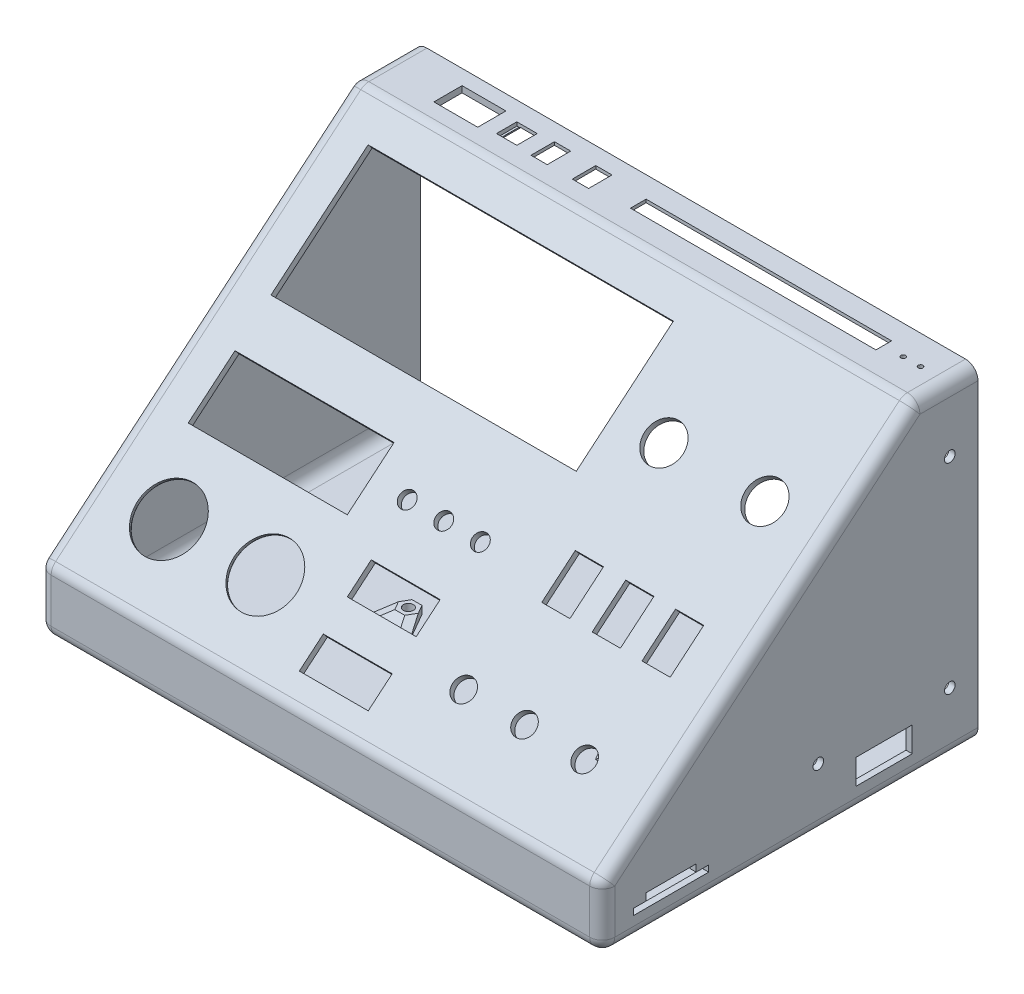
SolidWorks part; units mm, degrees
ref_plane "Front Plane" through (0, 0, 0) normal (0, 0, 1) x (1, 0, 0)
ref_plane "Top Plane" through (0, 0, 0) normal (0, 1, 0) x (1, 0, 0)
ref_plane "Right Plane" through (0, 0, 0) normal (1, 0, 0) x (0, 0, -1)
sketch "Sketch1" plane through (0, 0, 0) normal (0, 1, 0) x (1, 0, 0)
  line L1 (-90, -60) -> (90, -60)
  line L2 (-90, -60) -> (-90, 60)
  line L3 (-90, 60) -> (90, 60)
  line L4 (90, -60) -> (90, 60)
  line L5 (-90, -60) -> (90, 60) construction
  line L6 (-90, 60) -> (90, -60) construction
  point P0 (0, 0)
  dimension "D1" = 180
  dimension "D2" = 120
extrude "Boss-Extrude1" add sketch "Sketch1" along normal blind 20
sketch "Sketch2" plane through (-90, 0, 0) normal (-1, 0, 0) x (0, 0, 1)
  line L0 (60, 20) -> (-40, 103.91)
  line L1 (-60, 20) -> (60, 20) construction
  line L2 (60, 20) -> (60, 0) construction
  line L3 (-60, 20) -> (-60, 103.91)
  line L4 (-60, 103.91) -> (-40, 103.91)
  line L5 (-60, 20) -> (60, 20)
  dimension "D1" = 40
  dimension "D2" = 100
extrude "Boss-Extrude2" add sketch "Sketch2" against normal up to surface (180 mm away) up to face at (90, 10, 0)
shell "Shell3" thickness 2 removed face at (0, 51.955, -60)
fillet "Fillet1" radius 4 11 edges at (-90, 10, 60) (90, 10, 60) (0, 0, 60) (0, 20, 60) (-90, 61.955, 10) (0, 103.91, -40) (90, 61.955, 10) (-90, 103.91, -50) (-90, 0, 0) (90, 0, 0) (90, 103.91, -50)
fillet "Fillet2" radius 4 11 edges at (88, 10.5337, 58) (0, 19.0674, 58) (-88, 10.5337, 58) (0, 2, 58) (88, 101.91, -50.364) (0, 101.91, -40.7279) (-88, 101.91, -50.364) (88, 60.4887, 8.636) (88, 2, -1) (-88, 60.4887, 8.636) (-88, 2, -1)
sketch "Sketch7" plane through (0, 103.91, 0) normal (0, 1, 0) x (1, 0, 0)
  line L0 (-86, 60) -> (-86, 41.4559) construction
  line L1 (-86, 41.4559) -> (-86, 50.7279) construction
  line L2 (-86, 50.7279) -> (-56, 50.7279) construction
  line L3 (-56, 46.2279) -> (-56, 55.2279)
  line L4 (-56, 55.2279) -> (-70, 55.2279)
  line L5 (-70, 55.2279) -> (-70, 46.2279)
  line L6 (-70, 46.2279) -> (-56, 46.2279)
  point P9 (-56, 50.7279)
  dimension "D1" = 9
  dimension "D2" = 14
  dimension "D3" = 30
extrude "Cut-Extrude3" cut sketch "Sketch7" against normal up to next
sketch "Sketch8" plane through (0, 41.2807, 34.6386) normal (0, 0.766, 0.6428) x (1, 0, 0)
  line L0 (-86, 95.9779) -> (86, 95.9779) construction
  line L1 (86, 95.9779) -> (86, -31.2417) construction
  line L2 (86, -31.2417) -> (-86, -31.2417) construction
  line L3 (-86, -31.2417) -> (-86, 95.9779) construction
  line L4 (-76, 95.9779) -> (-76, -31.2417)
  line L5 (-86, 85.9779) -> (86, 85.9779)
  line L6 (86, -31.2417) -> (86, 95.9779) construction
  line L7 (-86, -31.2417) -> (86, -31.2417) construction
  line L8 (76, -31.2417) -> (76, 95.9779)
  line L9 (86, -21.2417) -> (-86, -21.2417)
  line L10 (-86, 95.9779) -> (-86, -31.2417) construction
  line L11 (86, 95.9779) -> (-86, 95.9779) construction
  line L12 (-73.5, 95.9779) -> (-73.5, 93.4779)
  line L13 (-76, 85.9779) -> (21.5, 85.9779)
  line L14 (-76, 85.9779) -> (-76, 45.4779)
  line L15 (-76, 45.4779) -> (21.5, 45.4779)
  line L16 (21.5, 85.9779) -> (21.5, 45.4779)
  line L17 (-76, 85.9779) -> (21.5, 85.9779) construction
  line L18 (-27.25, 85.9779) -> (-27.25, 45.4779) construction
  line L19 (-45.177, 65.7279) -> (-9.323, 65.7279)
  circle A0 centre (-73.5, 93.4779) radius 1.35
  circle A1 centre (-73.5, 37.9779) radius 1.35
  circle A2 centre (19, 37.9779) radius 1.35
  circle A3 centre (19, 93.4779) radius 1.35
  point P36 (-27.25, 65.7279)
  dimension "D1" = 10
  dimension "D2" = 10
  dimension "D3" = 10
  dimension "D4" = 10
  dimension "D5" = 97.5
  dimension "D6" = 40.5
  dimension "D7" = 2.5
  dimension "D8" = 2.5
extrude "Boss-Extrude4" add sketch "Sketch8" against normal blind 5 contours A0 | A3 | A2 | A1
extrude "Cut-Extrude4" cut sketch "Sketch8<3>" against normal blind 5 contours L16 L5 L4 L15 region at (-27.25, 95.8676, -30.4155)
sketch "Sketch8<3>" plane through (0, 41.2807, 34.6386) normal (0, 0.766, 0.6428) x (1, 0, 0) same geometry as "Sketch8"
sketch "Sketch9" plane through (0, 41.2807, 34.6386) normal (0, 0.766, 0.6428) x (1, 0, 0)
  line L0 (-76, 85.9779) -> (-76, 30.4779)
  line L1 (-76, 45.4779) -> (21.5, 45.4779) construction
  line L3 (-76, 30.4779) -> (-25.2, 30.4779)
  line L4 (-76, 30.4779) -> (-76, 10.9779)
  line L5 (-76, 10.9779) -> (-25.2, 10.9779)
  line L6 (-25.2, 30.4779) -> (-25.2, 10.9779)
  dimension "D1" = 15
  dimension "D2" = 50.8
  dimension "D3" = 19.5
extrude "Cut-Extrude5" cut sketch "Sketch9" against normal blind 5 contours L6 L3 L4 L5 region at (-50.6, 54.6044, 18.7601)
sketch "Sketch10" plane through (0, 41.2807, 34.6386) normal (0, 0.766, 0.6428) x (1, 0, 0)
  line L0 (-25.2, 30.4779) -> (-25.2, 10.9779) construction
  line L1 (21.5, 45.4779) -> (21.5, 10.9779)
  line L2 (-25.2, 30.4779) -> (21.5, 30.4779) construction
  line L3 (21.5, 30.4779) -> (21.5, 10.9779) construction
  line L4 (21.5, 10.9779) -> (-25.2, 10.9779) construction
  line L5 (-13.525, 20.7279) -> (-1.85, 20.7279)
  line L6 (-1.85, 20.7279) -> (9.825, 20.7279)
  circle A0 centre (-1.85, 20.7279) radius 2.525
  circle A1 centre (-13.525, 20.7279) radius 2.525
  circle A2 centre (9.825, 20.7279) radius 2.525
  dimension "D1" = 9.75
extrude "Cut-Extrude6" cut sketch "Sketch10" against normal blind 5 contours A1 | A0 | A2 | A0 region at (9.825, 56.1815, 16.8806) region at (-1.85, 55.2932, 17.9392) region at (-15.9786, 54.6044, 18.7601)
sketch "Sketch11" plane through (0, 41.2807, 34.6386) normal (0, 0.766, 0.6428) x (1, 0, 0)
  line L0 (21.5, 85.9779) -> (21.5, 45.4779) construction
  line L1 (86, 95.9779) -> (-86, 95.9779) construction
  line L2 (21.5, 65.7279) -> (86, 65.7279) construction
  line L3 (86, -31.2417) -> (86, 95.9779) construction
  line L4 (86, 65.7279) -> (53.75, 65.7279) construction
  line L5 (53.75, 65.7279) -> (21.5, 65.7279) construction
  line L6 (69.875, 67.1029) -> (69.875, 54.8529)
  line L7 (86, 65.7279) -> (53.75, 65.7279) construction
  line L8 (53.75, 65.7279) -> (86, 65.7279) construction
  line L9 (86, 65.7279) -> (69.875, 65.7279) construction
  line L10 (69.875, 65.7279) -> (69.875, 60.9779) construction
  line L11 (53.75, 65.7279) -> (53.75, 56.7637)
  circle A0 centre (69.875, 60.9779) radius 6.125
  circle A1 centre (37.625, 60.9779) radius 6.125
  dimension "D1" = 12.25
  dimension "D2" = 35
extrude "Cut-Extrude7" cut sketch "Sketch11" against normal blind 5 contours A1 | L6 A0 | L6 A0 region at (72.4745, 80.4766, -12.0732) region at (67.2755, 80.4766, -12.0732) region at (37.625, 80.4766, -12.0732)
sketch "Sketch12" plane through (0, 41.2807, 34.6386) normal (0, 0.766, 0.6428) x (1, 0, 0)
  line L0 (-76, 10.9779) -> (-76, -4.0221)
  line L1 (-76, -31.2417) -> (-76, -16.2417)
  line L2 (-86, -31.2417) -> (86, -31.2417) construction
  line L3 (-76, -4.0221) -> (-76, -16.2417) construction
  line L4 (-25.2, 10.9779) -> (-25.2, -31.2417)
  line L5 (-25.2, 30.4779) -> (-25.2, 10.9779) construction
  line L6 (-25.2, -31.2417) -> (-25.2, -10.1319)
  line L7 (-25.2, -10.1319) -> (-76, -10.1319)
  line L8 (-50.6, -10.1319) -> (-76, -10.1319) construction
  line L9 (-76, -10.1319) -> (-63.3, -10.1319) construction
  line L10 (-63.3, -10.1319) -> (-63.3, -2.7605) construction
  line L11 (-63.3, -2.7605) -> (-63.3, -10.1319) construction
  line L12 (-63.3, -10.1319) -> (-50.6, -10.1319) construction
  line L13 (-50.6, -10.1319) -> (-25.2, -10.1319) construction
  line L14 (-37.9, -10.1319) -> (-37.9, -2.7605) construction
  circle A2 centre (-66, -10.1319) radius 10
  circle A3 centre (-35.2, -10.1319) radius 10
  dimension "D1" = 15
  dimension "D2" = 15
extrude "Cut-Extrude8" cut sketch "Sketch12" against normal blind 5 contours L7 A2 | L7 A3 | L7 A3 | L7 A2 region at (-66, 32.04, 45.6513) region at (-35.2, 37.4961, 39.1489) region at (-35.2, 32.04, 45.6513) region at (-66, 37.4961, 39.1489)
fillet "Fillet4" radius 1.5 2 edges at (-35.2, 26.8081, 48.775) (-66, 26.8081, 48.775)
sketch "Sketch13" plane through (0, 41.2807, 34.6386) normal (0, 0.766, 0.6428) x (1, 0, 0)
  line L0 (-25.2, -10.1319) -> (32.7814, -10.1319)
  line L1 (21.5, 45.4779) -> (21.5, -10.1319)
  line L2 (21.5, -10.1319) -> (-25.2, -10.1319) construction
  line L3 (-25.2, -10.1319) -> (21.5, -10.1319) construction
  line L4 (21.5, -10.1319) -> (-1.85, -10.1319) construction
  line L5 (-25.2, 10.9779) -> (21.5, 10.9779)
  line L6 (-1.85, -10.1319) -> (-1.85, 10.9779) construction
  line L7 (-12.85, -25.1319) -> (9.15, -25.1319)
  line L8 (-12.85, -5.1319) -> (9.15, -5.1319)
  line L9 (-12.85, -5.1319) -> (-12.85, 4.8681)
  line L10 (-12.85, 4.8681) -> (9.15, 4.8681)
  line L11 (9.15, -5.1319) -> (9.15, 4.8681)
  line L12 (-12.85, -5.1319) -> (9.15, 4.8681) construction
  line L13 (-12.85, 4.8681) -> (9.15, -5.1319) construction
  line L14 (9.15, -15.1319) -> (9.15, -25.1319)
  line L15 (-12.85, -15.1319) -> (9.15, -15.1319)
  line L16 (-12.85, -15.1319) -> (-12.85, -25.1319)
  circle A0 centre (-35.2, -10.1319) radius 10 construction
  point P11 (-1.85, 0.423)
  dimension "D1" = 22
  dimension "D2" = 10
  dimension "D3" = 5
extrude "Cut-Extrude9" cut sketch "Sketch13" against normal blind 5 contours L8 L11 L10 L9 | L15 L16 L7 L14 region at (-1.85, 28.3402, 50.0605) region at (-1.85, 41.1959, 34.7397)
sketch "Sketch15" plane through (0, 41.2807, 34.6386) normal (0, 0.766, 0.6428) x (1, 0, 0)
  line L0 (21.5, 45.4779) -> (21.9808, 0)
  line L1 (21.5, 45.4779) -> (86, 45.4779) construction
  line L2 (86, -31.2417) -> (86, 95.9779) construction
  line L3 (86, 45.4779) -> (86, 0) construction
  line L4 (86, 0) -> (21.9808, 0) construction
  line L5 (86, 22.739) -> (21.7404, 22.739) construction
  line L6 (53.8702, 22.739) -> (86, 22.739) construction
  line L7 (49.3702, 15.739) -> (58.3702, 15.739)
  line L8 (49.3702, 15.739) -> (49.3702, 29.739)
  line L9 (49.3702, 29.739) -> (58.3702, 29.739)
  line L10 (58.3702, 15.739) -> (58.3702, 29.739)
  line L11 (49.3702, 15.739) -> (58.3702, 29.739) construction
  line L12 (49.3702, 29.739) -> (58.3702, 15.739) construction
  line L13 (86, 22.739) -> (69.9351, 22.739) construction
  line L14 (69.9351, 22.739) -> (69.9351, 40.2733) construction
  line L15 (69.9351, 40.2733) -> (69.9351, 22.739) construction
  line L16 (69.9351, 22.739) -> (53.8702, 22.739) construction
  line L17 (53.8702, 22.739) -> (21.7404, 22.739) construction
  line L18 (21.7404, 22.739) -> (37.8053, 22.739) construction
  line L19 (37.8053, 22.739) -> (37.8053, 31.5062) construction
  line L20 (33.1892, 15.833) -> (42.1892, 15.833)
  line L21 (33.1892, 15.833) -> (33.1892, 29.833)
  line L22 (33.1892, 29.833) -> (42.1892, 29.833)
  line L23 (42.1892, 15.833) -> (42.1892, 29.833)
  line L24 (65.3123, 15.6839) -> (74.3123, 15.6839)
  line L25 (65.3123, 15.6839) -> (65.3123, 29.6839)
  line L26 (65.3123, 29.6839) -> (74.3123, 29.6839)
  line L27 (74.3123, 15.6839) -> (74.3123, 29.6839)
  point P9 (53.8702, 22.739)
  dimension "D1" = 9
  dimension "D2" = 14
extrude "Cut-Extrude11" cut sketch "Sketch15" against normal blind 3.2 contours L24 L27 L26 L25 | L7 L10 L9 L8 | L20 L23 L22 L21 region at (53.8702, 55.897, 17.2196) region at (37.6892, 55.9575, 17.1476) region at (69.8123, 55.8616, 17.2618)
sketch "Sketch16" plane through (0, 41.2807, 34.6386) normal (0, 0.766, 0.6428) x (1, 0, 0)
  line L0 (9.15, 4.8681) -> (9.15, -25.1319) construction
  line L1 (9.15, -25.1319) -> (9.15, -10.1319) construction
  line L2 (9.15, -10.1319) -> (86, -10.1319) construction
  line L3 (86, -31.2417) -> (86, 95.9779) construction
  line L4 (47.575, -10.1319) -> (86, -10.1319) construction
  line L5 (86, -10.1319) -> (47.575, -10.1319) construction
  line L6 (47.575, -10.1319) -> (9.15, -10.1319) construction
  line L7 (47.575, -10.1319) -> (86, -10.1319) construction
  circle A0 centre (66.7875, -10.1319) radius 3.5
  circle A1 centre (47.575, -10.1319) radius 3.5
  circle A2 centre (28.1503, -10.1319) radius 3.5
extrude "Cut-Extrude12" cut sketch "Sketch16" against normal blind 3.2 contours A0 | A2 | A1 region at (66.7875, 34.7681, 42.4001)
sketch "Sketch17" plane through (0, 0, 0) normal (0, -1, 0) x (1, 0, 0)
  line L0 (-86, 56) -> (-78.2218, 48.2218)
  line L1 (0, 0) -> (25.5086, 0)
  line L2 (57.1505, 0) -> (-57.1505, 0) construction
  line L3 (25.5086, 0) -> (0, 0)
  line L4 (0, 0) -> (0, 11.6481)
  line L5 (0, 0) -> (0, -3.057)
  line L6 (0, -3.057) -> (9.4489, -3.057)
  line L7 (0, -1.5285) -> (4.9263, -1.5285)
  circle A0 centre (-78.2218, 48.2218) radius 6
  circle A1 centre (-78.2218, 48.2218) radius 7
  circle A2 centre (78.2218, 48.2218) radius 7
  circle A3 centre (78.2218, 48.2218) radius 6
  circle A4 centre (78.2218, -51.2788) radius 7
  circle A5 centre (78.2218, -51.2788) radius 6
  circle A6 centre (-78.2218, -51.2788) radius 7
  circle A7 centre (-78.2218, -51.2788) radius 6
  dimension "D1" = 11
extrude "Boss-Extrude5" add sketch "Sketch17" along normal blind 0.5 contours A4 A5 | A2 A3 | A1 A0 | A6 A7 region at (-75.6188, 0, 54.5061) region at (71.4198, 0, 48.2218) region at (71.4198, 0, -51.2788) region at (-85.0238, 0, -51.2788)
fillet "Fillet7" radius 0.5 8 edges at (78.2218, -0.5, -58.2788) (78.2218, -0.5, -57.2788) (-78.2218, -0.5, -57.2788) (-78.2218, -0.5, -58.2788) (-78.2218, -0.5, 41.2218) (-78.2218, -0.5, 42.2218) (78.2218, -0.5, 42.2218) (78.2218, -0.5, 41.2218)
sketch "Sketch18" plane through (0, 101.91, 0) normal (0, -1, 0) x (1, 0, 0)
  line L0 (-56, -50.7279) -> (-51, -50.7279)
  line L1 (-56, -55.2279) -> (-56, -46.2279) construction
  line L2 (-51, -50.7279) -> (-51, -44.1838)
  line L3 (-51, -44.1838) -> (-51, -50.7279)
  line L4 (-51, -50.7279) -> (-51, -58)
  line L5 (84, -60) -> (-84, -60) construction
  line L6 (-51, -58) -> (79, -58)
  line L7 (-51, -58) -> (-51, -44.1838)
  line L8 (-51, -44.1838) -> (79, -44.1838)
  line L9 (79, -58) -> (79, -44.1838)
  line L10 (84, -42.1838) -> (-84, -42.1838) construction
  line L11 (84, -60) -> (84, -42.1838) construction
  dimension "D1" = 5
  dimension "D2" = 2
  dimension "D3" = 2
  dimension "D4" = 5
extrude "Cut-Extrude13" cut sketch "Sketch18" against normal blind 1 contours L6 L9 L8 L2 L4 region at (14, 101.91, -51.0919)
fillet "Fillet8" radius 1 4 edges at (-51, 102.91, -51.0919) (14, 102.91, -44.1838) (79, 102.91, -51.0919) (14, 102.91, -58)
sketch "Sketch19" plane through (0, 103.91, 0) normal (0, 1, 0) x (1, 0, 0)
  line L0 (-56, 50.7279) -> (-48, 50.7279)
  line L2 (-46, 50.7279) -> (-35, 50.7279)
  line L3 (-35, 50.7279) -> (-37.4401, 50.7279)
  line L4 (-34.55, 54.4779) -> (-39.75, 54.4779)
  line L5 (-34.55, 54.4779) -> (-34.55, 46.9779)
  line L6 (-34.55, 46.9779) -> (-39.75, 46.9779)
  line L7 (-39.75, 54.4779) -> (-39.75, 46.9779)
  line L8 (-34.55, 54.4779) -> (-39.75, 46.9779) construction
  line L9 (-34.55, 46.9779) -> (-39.75, 54.4779) construction
  line L10 (-29.2247, 50.7279) -> (-9.2247, 50.7279)
  line L14 (-34.1901, 47.4779) -> (-34.1901, 53.9779)
  line L15 (-40.6901, 47.4779) -> (-34.1901, 53.9779) construction
  line L16 (-40.6901, 53.9779) -> (-34.1901, 47.4779) construction
  line L17 (-9.2247, 50.7279) -> (-9.2247, 53.2279)
  line L18 (-9.2247, 53.2279) -> (69.1753, 53.2279)
  line L19 (69.1753, 53.2279) -> (69.1753, 48.2279)
  line L20 (69.1753, 48.2279) -> (-9.2247, 48.2279)
  line L21 (-9.2247, 48.2279) -> (-9.2247, 50.7279)
  line L22 (69.1753, 50.7279) -> (87.1753, 50.7279)
  line L23 (87.1753, 50.7279) -> (69.1753, 50.7279) construction
  line L24 (75.4253, 50.7279) -> (80.9253, 50.7279)
  line L26 (-29.2247, 50.7279) -> (-23.95, 50.7279)
  line L27 (-56, 55.2279) -> (-56, 46.2279) construction
  line L28 (-26.55, 46.9779) -> (-21.35, 46.9779)
  line L29 (-26.55, 46.9779) -> (-26.55, 54.4779)
  line L30 (-26.55, 54.4779) -> (-21.35, 54.4779)
  line L31 (-21.35, 46.9779) -> (-21.35, 54.4779)
  line L32 (-26.55, 46.9779) -> (-21.35, 54.4779) construction
  line L33 (-26.55, 54.4779) -> (-21.35, 46.9779) construction
  line L34 (-56, 46.2279) -> (-56, 55.2279) construction
  line L36 (-51.25, 47.4779) -> (-44.75, 47.4779)
  line L37 (-51.25, 47.4779) -> (-51.25, 53.9779)
  line L38 (-51.25, 53.9779) -> (-44.75, 53.9779)
  line L39 (-44.75, 47.4779) -> (-44.75, 53.9779)
  line L40 (-51.25, 47.4779) -> (-44.75, 53.9779) construction
  line L41 (-51.25, 53.9779) -> (-44.75, 47.4779) construction
  circle A0 centre (75.4253, 50.7279) radius 0.75
  circle A1 centre (80.9253, 50.7279) radius 0.75
  point P25 (78.1753, 50.7279)
  dimension "D12" = 9
  dimension "D2" = 3.75
  dimension "D3" = 5.2
  dimension "D4" = 21
  dimension "D5" = 6.5
  dimension "D6" = 6.5
  dimension "D8" = 5
  dimension "D9" = 2.5
  dimension "D10" = 78.4
  dimension "D11" = 5.5
  dimension "D13" = 5.2
  dimension "D14" = 3.75
  dimension "D15" = 6.5
  dimension "D16" = 6.5
  dimension "D17" = 8
  dimension "D18" = 5
  dimension "D19" = 8
  dimension "D20" = 12.1253
extrude "Cut-Extrude14" cut sketch "Sketch19" against normal blind 1.2 contours L21 L20 L19 L18 L17 | L14 | L2 L7 L6 L5 L3 | L4 L7 L2 L3 L5 | A0 | A1 | L37 L36 L39 L38 | L29 L28 L31 L30 region at (-39.6587, 103.91, -52.6029) region at (29.9753, 103.91, -50.7279)
sketch "Sketch20" plane through (-90, 0, 0) normal (-1, 0, 0) x (0, 0, 1)
  line L0 (-60, 99.91) -> (-45, 99.91)
  line L1 (-41.4559, 99.91) -> (-60, 99.91) construction
  line L2 (-45, 99.91) -> (-45, 84.91)
  line L3 (-45, 84.91) -> (-60, 84.91)
  line L4 (-60, 99.91) -> (-60, 4) construction
  line L5 (-60, 84.91) -> (-60, 99.91)
  line L6 (-60, 99.91) -> (-41.4559, 99.91) construction
  line L7 (-52.5, 99.91) -> (-52.5, 84.91)
  circle A0 centre (-52.5, 92.41) radius 6
  dimension "D1" = 15
  dimension "D2" = 15
extrude "Cut-Extrude15" cut sketch "Sketch20" against normal blind 10 contours L7 A0 | L7 A0 region at (-90, 92.41, -49.9535) region at (-90, 92.41, -55.0465)
sketch "Sketch21" plane through (0, 0, -60) normal (0, 0, -1) x (-1, 0, 0)
  line L0 (-83, 101.91) -> (-84, 101.91)
  line L1 (-84, 101.91) -> (84, 101.91) construction
  line L2 (-88, 97.91) -> (-88, 96.91)
  line L3 (-88, 97.91) -> (-88, 6) construction
  line L4 (-88, 96.91) -> (-88, 97.91)
  line L5 (-83, 101.91) -> (-83, 96.91)
  line L6 (-83, 96.91) -> (-88, 96.91)
  arc A0 (-88, 97.91) -> (-84, 101.91) centre (-84, 97.91) cw
  line M13 (-88, 6) -> (-88, 97.91)
  arc M14 (-88, 97.91) -> (-84, 101.91) centre (-84, 97.91) cw
  line M15 (-84, 101.91) -> (84, 101.91)
  dimension "D1" = 1
  dimension "D2" = 1
extrude "Boss-Extrude6" add sketch "Sketch21" against normal up to next contours L6 L5 M15 M14 M13 region at (85.2442, 99.1542, -60)
sketch "Sketch22" plane through (0, 0, -60) normal (0, 0, -1) x (-1, 0, 0)
  line L0 (-83, 96.91) -> (-85.5456, 99.4555)
  circle A0 centre (-85.5456, 99.4555) radius 1.6
  dimension "D1" = 3.6
extrude "Cut-Extrude16" cut sketch "Sketch22" against normal blind 16 contours A0 region at (84.1092, 98.8606, -60)
fillet "Fillet9" radius 1 1 edges at (83, 96.91, -47.3846)
sketch "Sketch4" plane through (0, 2, 0) normal (0, 1, 0) x (1, 0, 0)
  line L0 (-84, -54) -> (84, -54) construction
  line L1 (0, -54) -> (0, 60) construction
  line L2 (84, 60) -> (-84, 60) construction
  line L3 (0, -54) -> (0, 60) construction
  line L5 (41.275, 50) -> (-41.275, 50)
  line L6 (41.275, 50) -> (41.275, 1.74)
  line L7 (41.275, 1.74) -> (-41.275, 1.74)
  line L8 (-41.275, 50) -> (-41.275, 1.74)
  line L9 (41.275, 50) -> (-41.275, 1.74) construction
  line L10 (41.275, 1.74) -> (-41.275, 50) construction
  line L15 (38.0996, 1.74) -> (39.6873, -1.01)
  line L16 (39.6873, -1.01) -> (42.8627, -1.01)
  line L17 (42.8627, -1.01) -> (44.4504, 1.74)
  line L18 (44.4504, 1.74) -> (42.8627, 4.49)
  line L25 (42.8627, 4.49) -> (39.6873, 4.49)
  line L44 (39.6873, 4.49) -> (38.0996, 1.74)
  line L45 (38.0996, 50) -> (39.6873, 47.25)
  line L46 (39.6873, 47.25) -> (42.8627, 47.25)
  line L47 (42.8627, 47.25) -> (44.4504, 50)
  line L48 (44.4504, 50) -> (42.8627, 52.75)
  line L49 (42.8627, 52.75) -> (39.6873, 52.75)
  line L50 (39.6873, 52.75) -> (38.0996, 50)
  line L51 (-38.0996, 50) -> (-39.6873, 52.75)
  line L52 (-39.6873, 52.75) -> (-42.8627, 52.75)
  line L53 (-42.8627, 52.75) -> (-44.4504, 50)
  line L54 (-44.4504, 50) -> (-42.8627, 47.25)
  line L55 (-42.8627, 47.25) -> (-39.6873, 47.25)
  line L56 (-39.6873, 47.25) -> (-38.0996, 50)
  line L57 (-30.4796, 1.74) -> (-32.0673, 4.49)
  line L58 (-32.0673, 4.49) -> (-35.2427, 4.49)
  line L59 (-35.2427, 4.49) -> (-36.8304, 1.74)
  line L60 (-36.8304, 1.74) -> (-35.2427, -1.01)
  line L61 (-35.2427, -1.01) -> (-32.0673, -1.01)
  line L62 (-32.0673, -1.01) -> (-30.4796, 1.74)
  circle A1 centre (41.275, 1.74) radius 2.75 construction
  circle A2 centre (41.275, 50) radius 2.75 construction
  circle A3 centre (-41.275, 50) radius 2.75 construction
  circle A4 centre (-33.655, 1.74) radius 2.75 construction
  point P8 (0.5325, 6.382)
  dimension "D1" = 82.55
  dimension "D2" = 48.26
  dimension "D3" = 74.93
  dimension "D4" = 10
extrude "Boss-Extrude7" add sketch "Sketch4" along normal blind 2.5 contours L54 L55 L8 L5 L51 L52 L53 | L61 L62 L7 L60 | L58 L59 L7 L57 | L25 L44 L7 L6 | L18 L25 L6 L7 L15 L16 L17 | L49 L50 L5 L6 L46 L47 L48 | L45 L46 L6 L5 | L55 L56 L5 L8 region at (40.0401, 2, -48.7778) region at (41.6866, 2, -50.4074) region at (-40.0401, 2, -48.7778) region at (-41.6866, 2, -50.4074) region at (41.6866, 2, -1.3326) region at (40.0401, 2, -2.9622) region at (-33.655, 2, -0.5178) region at (-33.655, 2, -2.9622)
sketch "Sketch23" plane through (0, 4.5, 0) normal (0, 1, 0) x (1, 0, 0)
  line L0 (42.8627, -1.01) -> (39.6873, 4.49) construction
  line L1 (38.0996, 1.74) -> (-30.4796, 1.74) construction
  line L2 (-38.0996, 50) -> (38.0996, 50) construction
  line L3 (-38.0996, 50) -> (-39.6873, 52.75) construction
  line L4 (38.0996, 50) -> (0, 50) construction
  line L5 (3.81, 1.74) -> (3.81, 50) construction
  line L6 (15.6177, 25.87) -> (-7.9977, 25.87)
  line L7 (0, 50) -> (0, 19.7968)
  line L8 (38.0996, 50) -> (-38.0996, 50) construction
  line L9 (-39.6873, 47.25) -> (-42.8627, 52.75) construction
  line L10 (42.8627, 47.25) -> (39.6873, 52.75) construction
  circle A0 centre (41.275, 1.74) radius 1.6
  circle A1 centre (-33.655, 1.74) radius 1.6
  circle A2 centre (41.275, 50) radius 1.6
  circle A3 centre (-41.275, 50) radius 1.6
  point P23 (3.81, 25.87)
  point P32 (41.275, 50)
extrude "Cut-Extrude17" cut sketch "Sketch23" against normal blind 3 contours A3 | A2 | A0 | A1 region at (-41.275, 4.5, -50)
chamfer "Chamfer1" distance 2.5 angle 70 12 edges at (43.6566, 2, -0.365) (38.8934, 2, -0.365) (41.275, 2, 1.01) (43.6566, 2, -48.625) (41.275, 2, -47.25) (38.8934, 2, -48.625) (-31.2734, 2, -0.365) (-36.0366, 2, -0.365) (-33.655, 2, 1.01) (-43.6566, 2, -48.625) (-41.275, 2, -47.25) (-38.8934, 2, -48.625) first distance on face at (43.6566, 3.25, -0.365) first distance on face at (38.8934, 3.25, -0.365) first distance on face at (41.275, 3.25, 1.01) first distance on face at (43.6566, 3.25, -48.625) first distance on face at (41.275, 3.25, -47.25) first distance on face at (38.8934, 3.25, -48.625) first distance on face at (-31.2734, 3.25, -0.365) first distance on face at (-36.0366, 3.25, -0.365) first distance on face at (-33.655, 3.25, 1.01) first distance on face at (-43.6566, 3.25, -48.625) first distance on face at (-41.275, 3.25, -47.25) first distance on face at (-38.8934, 3.25, -48.625)
sketch "Sketch25" plane through (88, 0, 0) normal (-1, 0, 0) x (0, 0, 1)
  line L0 (54, 6) -> (50, 6)
  line L1 (-60, 6) -> (54, 6) construction
  line L2 (50, 6) -> (50, 7)
  line L3 (50, 7) -> (26, 7)
  line L4 (26, 7) -> (26, 9)
  line L5 (26, 9) -> (30, 9)
  line L6 (30, 9) -> (30, 11.3)
  line L7 (30, 11.3) -> (46, 11.3)
  line L8 (46, 11.3) -> (46, 9)
  line L9 (46, 9) -> (50, 9)
  line L10 (50, 9) -> (50, 7)
  point P5 (50, 8)
  dimension "D1" = 24
  dimension "D2" = 4
  dimension "D3" = 4
  dimension "D4" = 2
  dimension "D5" = 2.3
  dimension "D6" = 4
  dimension "D7" = 1
  dimension "D8" = 2
extrude "Cut-Extrude18" cut sketch "Sketch25" against normal blind 3 contours L3 L4 L5 L6 L7 L8 L9 L10
sketch "Sketch26" plane through (88, 0, 0) normal (-1, 0, 0) x (0, 0, 1)
  line L0 (-60, 96.91) -> (-60, 6) construction
  line L1 (-60, 51.455) -> (-30, 51.455)
  line L2 (-55, 16.455) -> (-51, 16.455)
  line L3 (-55, 16.455) -> (-5, 16.455)
  line L4 (-55, 16.455) -> (-55, 86.455)
  line L5 (-55, 86.455) -> (-5, 86.455)
  line L6 (-5, 16.455) -> (-5, 86.455)
  line L7 (-55, 16.455) -> (-5, 86.455) construction
  line L8 (-55, 86.455) -> (-5, 16.455) construction
  line L9 (-51, 16.455) -> (-51, 19.455)
  line L10 (-30, 16.455) -> (-30, 25.2168)
  line L11 (-30, 16.455) -> (-30, 6) construction
  line L12 (-60, 6) -> (54, 6) construction
  line L14 (-39, 15.2275) -> (-21, 15.2275)
  line L15 (-39, 15.2275) -> (-39, 7.2275)
  line L16 (-39, 7.2275) -> (-21, 7.2275)
  line L17 (-21, 15.2275) -> (-21, 7.2275)
  line L18 (-39, 15.2275) -> (-21, 7.2275) construction
  line L19 (-39, 7.2275) -> (-21, 15.2275) construction
  circle A0 centre (-51, 19.455) radius 1.7
  circle A1 centre (-9, 19.455) radius 1.7
  circle A2 centre (-51, 83.455) radius 1.7
  point P17 (-30, 11.2275)
  dimension "D6" = 18
  dimension "D1" = 50
  dimension "D2" = 70
  dimension "D3" = 30
  dimension "D4" = 3
  dimension "D5" = 4
  dimension "D7" = 8
extrude "Cut-Extrude19" cut sketch "Sketch26" against normal blind 10 contours A0 | A1 | L17 L14 L15 L16 | A2 region at (88, 20.6231, -52.1681) region at (88, 11.2275, -30) region at (88, 19.455, -9)
